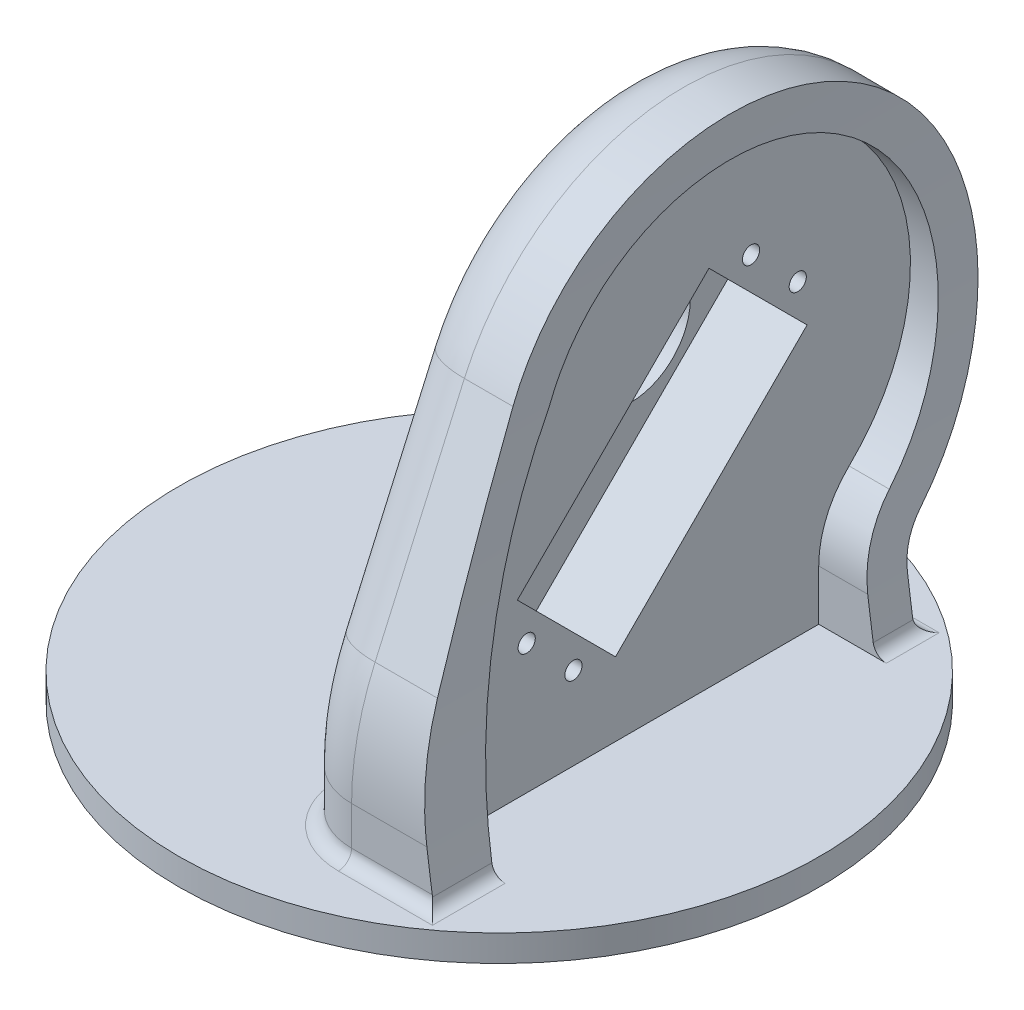
SolidWorks part; units mm, degrees
ref_plane "Front Plane" through (0, 0, 0) normal (0, 0, 1) x (1, 0, 0)
ref_plane "Top Plane" through (0, 0, 0) normal (0, 1, 0) x (1, 0, 0)
ref_plane "Right Plane" through (0, 0, 0) normal (1, 0, 0) x (0, 0, -1)
sketch "Sketch2" plane through (0, 0, 0) normal (0, 1, 0) x (1, 0, 0)
  line L0 (0, -7.25) -> (0, 7.25) construction
  circle A0 centre (0, 0) radius 48.5
  circle A1 centre (0, 7.25) radius 1.5
  circle A2 centre (0, -7.25) radius 1.5
  point P6 (0, 0)
  dimension "D2" = 97
  dimension "D3" = 3
  dimension "D1" = 14.5
extrude "Boss-Extrude1" add sketch "Sketch2" along normal blind 4
sketch "Sketch3" plane through (0, 4, 0) normal (0, 1, 0) x (1, 0, 0)
  circle A0 centre (0, 0) radius 3.75
  dimension "D1" = 7.5
extrude "Cut-Extrude1" cut sketch "Sketch3" against normal blind 1.5 from offset 2.5 offset against normal yes
sketch "Sketch4" plane through (0, 0, 0) normal (1, 0, 0) x (0, 0, -1)
  line L0 (-30.34, 4) -> (30.34, 4)
  line L1 (48.5, 4) -> (-48.5, 4) construction
  line L2 (30.34, 4) -> (30.34, 11.64)
  line L3 (-30.34, 4) -> (-30.34, 11.86)
  line L4 (-13.7924, 56.5853) -> (-27.3065, 26.1616)
  arc A0 (30.34, 11.64) -> (34.9356, 22.445) centre (45.34, 11.64) cw
  arc A1 (34.9356, 22.445) -> (-13.7924, 56.5853) centre (13.91, 44.28) ccw
  arc A2 (-30.34, 11.86) -> (-27.3065, 26.1616) centre (4.89, 11.86) cw
  circle A3 centre (13.91, 44.28) radius 9
  point P5 (0, 4)
  point P11 (0, 0)
  dimension "D3" = 15
  dimension "D5" = 35.23
  dimension "D6" = 18
  dimension "D1" = 60.68
  dimension "D2" = 7.64
  dimension "D4" = 7.86
  dimension "D7" = 13.91
  dimension "D8" = 40.28
extrude "Boss-Extrude2" add sketch "Sketch4" along normal blind 14 from offset 4
sketch "Sketch5" plane through (0, 0, 0) normal (1, 0, 0) x (0, 0, -1)
  line L0 (-0.41, 15.11) -> (28.5814, 44.1014)
  line L1 (-0.41, 15.11) -> (-15.2592, 29.9592)
  line L2 (28.5814, 44.1014) -> (13.7321, 58.9506)
  line L3 (-15.2592, 29.9592) -> (13.7321, 58.9506)
  line L5 (48.5, 4) -> (-48.5, 4) construction
  line L6 (-30.34, 4) -> (30.34, 4) construction
  line L7 (-0.7636, 44.4549) -> (14.0857, 29.6057) construction
  line L8 (6.6611, 37.0303) -> (23.6316, 54.0009) construction
  line L9 (20.0961, 57.5364) -> (27.1672, 50.4653)
  circle A0 centre (20.0961, 57.5364) radius 1.3
  circle A1 centre (27.1672, 50.4653) radius 1.3
  circle A2 centre (-6.774, 16.5242) radius 1.3
  circle A3 centre (-13.845, 23.5953) radius 1.3
  point P16 (23.6316, 54.0009)
  dimension "D8" = 2.6
  dimension "D1" = 0.41
  dimension "D2" = 11.11
  dimension "D3" = 41
  dimension "D4" = 21
  dimension "D5" = 45
  dimension "D6" = 3.5
  dimension "D7" = 10
extrude "Cut-Extrude2" cut sketch "Sketch5" along normal through all from offset 6 contours L3 L1 L0 L2 | A1 | A0 | A2 | A3 region at (0, 37.0303, -6.6611) region at (0, 51.6324, -27.6506)
sketch "Sketch6" plane through (18, 0, 0) normal (1, 0, 0) x (0, 0, -1)
  line L0 (33.34, 4) -> (33.34, 11.64) construction
  line L1 (-16.534, 57.8032) -> (-30.0482, 27.3795) construction
  line L2 (-33.34, 11.86) -> (-33.34, 4) construction
  line L3 (36.34, 4) -> (36.34, 11.64)
  line L4 (30.34, 4) -> (30.34, 11.64)
  line L5 (-13.7924, 56.5853) -> (-27.3065, 26.1616)
  line L6 (-30.34, 11.86) -> (-30.34, 4)
  line L7 (-30.34, 4) -> (30.34, 4)
  line L8 (30.34, 4) -> (30.34, 11.64)
  line L11 (-27.34, 4) -> (30.34, 4)
  line L12 (-19.2757, 59.021) -> (-32.7899, 28.5973)
  line L13 (-36.34, 11.86) -> (-36.34, 4)
  line L14 (-30.34, 4) -> (30.34, 4) construction
  line L15 (-36.34, 4) -> (-27.34, 4)
  line L16 (-13.7924, 56.5853) -> (-27.3065, 26.1616) construction
  line L17 (-30.34, 11.86) -> (-30.34, 4) construction
  line L20 (30.34, 4) -> (36.34, 4)
  arc A0 (37.0165, 20.284) -> (33.34, 11.64) centre (45.34, 11.64) ccw construction
  arc A1 (37.0165, 20.284) -> (-16.534, 57.8032) centre (13.91, 44.28) ccw construction
  arc A2 (-30.0482, 27.3795) -> (-33.34, 11.86) centre (4.89, 11.86) ccw construction
  arc A3 (34.9356, 22.445) -> (30.34, 11.64) centre (45.34, 11.64) ccw
  arc A4 (34.9356, 22.445) -> (-13.7924, 56.5853) centre (13.91, 44.28) ccw
  arc A5 (-27.3065, 26.1616) -> (-30.34, 11.86) centre (4.89, 11.86) ccw
  arc A6 (34.9356, 22.445) -> (30.34, 11.64) centre (45.34, 11.64) ccw
  arc A7 (34.9356, 22.445) -> (-13.7924, 56.5853) centre (13.91, 44.28) ccw
  arc A9 (39.0973, 18.123) -> (36.34, 11.64) centre (45.34, 11.64) ccw
  arc A10 (39.0973, 18.123) -> (-19.2757, 59.021) centre (13.91, 44.28) ccw
  arc A11 (-32.7899, 28.5973) -> (-36.34, 11.86) centre (4.89, 11.86) ccw
  arc A12 (-13.7924, 56.5853) -> (-27.34, 4) centre (72.634, 6.2814) ccw
  arc A13 (-27.3065, 26.1616) -> (-30.34, 11.86) centre (4.89, 11.86) ccw construction
  line M21 (30.34, 4) -> (30.34, 11.64)
  arc M22 (30.34, 11.64) -> (34.9356, 22.445) centre (45.34, 11.64) cw
  arc M23 (34.9356, 22.445) -> (-13.7924, 56.5853) centre (13.91, 44.28) ccw
  line M24 (-13.7924, 56.5853) -> (-27.3065, 26.1616)
  arc M25 (-27.3065, 26.1616) -> (-30.34, 11.86) centre (4.89, 11.86) ccw
  line M26 (-30.34, 11.86) -> (-30.34, 4)
  line M27 (-30.34, 4) -> (30.34, 4)
  dimension "D4" = 3
  dimension "D5" = 100
  dimension "D1" = 0
  dimension "D2" = 3
  dimension "D3" = 3
extrude "Boss-Extrude3" add sketch "Sketch6" along normal blind 9 and the other way up to surface (14 mm away) contours A12 L20 L3 A9 A10 L12 A11 L13 L15 M23 M22 M21 M26 M25 M24 | A12 M24 M25 M26 M27 region at (18, 5.1558, -33.34) region at (18, 16.4925, 27.9227) other way up to face at (4, 23.8443, -1.8168)
sketch "Sketch7" plane through (0, 0, 0) normal (0, 0, 1) x (1, 0, 0)
  line L0 (27, 80.5924) -> (21, 80.5924)
  line L1 (27, 80.5924) -> (4, 80.5924) construction
  line L2 (4, 4) -> (27, 4) construction
  line L3 (26.5, 4) -> (27, 4)
  line L4 (27, 4) -> (27, 80.5924)
  arc A0 (21, 80.5924) -> (26.5, 4) centre (520.9933, 78.0026) ccw
  dimension "D3" = 500
  dimension "D1" = 6
  dimension "D2" = 0.5
extrude "Cut-Extrude3" cut sketch "Sketch7" against normal through all both and the other way through all
fillet "Fillet1" radius 10 6 edges at (4, 7.82, -36.34) (4, 15.1625, -37.058) (4, 7.93, 36.34) (4, 20.4149, 35.4427) (4, 43.8092, 26.0328) (4, 74.0194, -34.7464)
fillet "Fillet2" radius 2 5 edges at (20.25, 4, 36.34) (6.9289, 4, 33.4111) (20.25, 4, -36.34) (6.9289, 4, -33.4111) (4, 4, 0)
fillet "Fillet3" radius 2 2 edges at (26.5, 4, 32.84) (26.5, 4, -34.34)
